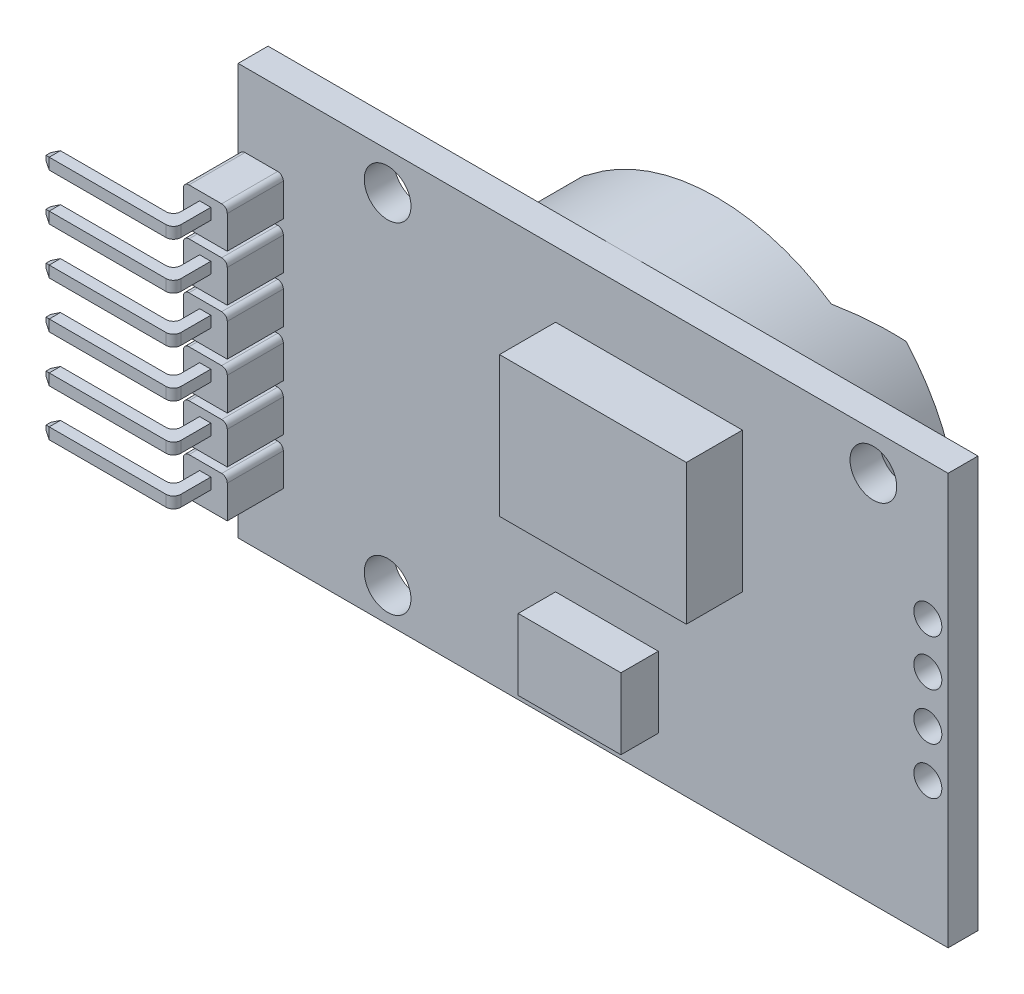
SolidWorks part; units mm, degrees
ref_plane "Front Plane" through (0, 0, 0) normal (0, 0, 1) x (1, 0, 0)
ref_plane "Top Plane" through (0, 0, 0) normal (0, 1, 0) x (1, 0, 0)
ref_plane "Right Plane" through (0, 0, 0) normal (1, 0, 0) x (0, 0, -1)
sketch "Sketch1" plane through (0, 0, 0) normal (0, 0, 1) x (1, 0, 0)
  line L1 (-19, -11) -> (19, -11)
  line L2 (-19, -11) -> (-19, 11)
  line L3 (-19, 11) -> (19, 11)
  line L4 (19, -11) -> (19, 11)
  line L5 (-19, -11) -> (19, 11) construction
  line L6 (-19, 11) -> (19, -11) construction
  point P0 (0, 0)
  dimension "D1" = 38
  dimension "D2" = 22
extrude "Boss-Extrude1" add sketch "Sketch1" along normal blind 1.6
sketch "Sketch2" plane through (0, 0, 1.6) normal (0, 0, 1) x (1, 0, 0)
  line L0 (19, -11) -> (19, 11) construction
  line L1 (-2.0099, 7.497) -> (7.9901, 7.497)
  line L2 (-2.0099, 7.497) -> (-2.0099, -0.003)
  line L3 (-2.0099, -0.003) -> (7.9901, -0.003)
  line L4 (7.9901, 7.497) -> (7.9901, -0.003)
  line L5 (-2.0099, -5.003) -> (3.4901, -5.003)
  line L6 (-2.0099, -5.003) -> (-2.0099, -8.803)
  line L7 (-2.0099, -8.803) -> (3.4901, -8.803)
  line L8 (3.4901, -5.003) -> (3.4901, -8.803)
  line L9 (19, 5) -> (16.8282, 5)
  line L10 (19, 5) -> (19, -5)
  line L11 (19, -5) -> (16.8282, -5)
  line L12 (16.8282, 5) -> (16.8282, -5)
  line L13 (-19, 11) -> (-19, -11) construction
  line L14 (-21.5, -7.5) -> (-16.5, -7.5)
  line L15 (-21.5, -7.5) -> (-21.5, 7.5)
  line L16 (-21.5, 7.5) -> (-16.5, 7.5)
  line L17 (-16.5, -7.5) -> (-16.5, 7.5)
  line L18 (-21.5, -7.5) -> (-16.5, 7.5) construction
  line L19 (-21.5, 7.5) -> (-16.5, -7.5) construction
  line L20 (19, 11) -> (-19, 11) construction
  line L21 (-21.5, -0.003) -> (-16.5, -0.003)
  line L22 (-21.5, 5) -> (-16.5, 5)
  line L23 (-21.5, 2.497) -> (-16.5, 2.497)
  line L24 (-21.5, -2.503) -> (-16.5, -2.503)
  line L25 (-21.5, -5.003) -> (-16.5, -5.003)
  line L26 (-18.9321, 4.25) -> (-18.9321, 2.5)
  line L27 (-16.8821, 7.05) -> (-18.6321, 7.05)
  line L28 (-16.5821, 6.75) -> (-16.5821, 5)
  line L29 (-16.8821, 4.7) -> (-18.6321, 4.7)
  line L30 (-18.9321, 6.75) -> (-18.9321, 5)
  line L31 (-16.8821, 2.2) -> (-18.6321, 2.2)
  line L32 (-16.5821, 4.25) -> (-16.5821, 2.5)
  line L33 (-16.8821, 4.55) -> (-18.6321, 4.55)
  line L34 (-18.9321, 1.75) -> (-18.9321, 0)
  line L35 (-16.8821, -0.3) -> (-18.6321, -0.3)
  line L36 (-16.5821, 1.75) -> (-16.5821, 0)
  line L37 (-16.8821, 2.05) -> (-18.6321, 2.05)
  line L38 (-18.9321, -0.75) -> (-18.9321, -2.5)
  line L39 (-16.8821, -2.8) -> (-18.6321, -2.8)
  line L40 (-16.5821, -0.75) -> (-16.5821, -2.5)
  line L41 (-16.8821, -0.45) -> (-18.6321, -0.45)
  line L42 (-18.9321, -3.25) -> (-18.9321, -5)
  line L43 (-16.8821, -5.3) -> (-18.6321, -5.3)
  line L44 (-16.5821, -3.25) -> (-16.5821, -5)
  line L45 (-16.8821, -2.95) -> (-18.6321, -2.95)
  line L46 (-18.9321, -5.75) -> (-18.9321, -7.5)
  line L47 (-16.8821, -7.8) -> (-18.6321, -7.8)
  line L48 (-16.5821, -5.75) -> (-16.5821, -7.5)
  line L49 (-16.8821, -5.45) -> (-18.6321, -5.45)
  line L50 (23.8182, -0.0985) -> (-35.2752, -0.0985) construction
  line L51 (16.8282, 2.5) -> (19, 2.5)
  line L52 (16.8282, 0) -> (19, 0)
  line L53 (16.8282, -2.5) -> (19, -2.5)
  line L54 (-19, 11) -> (19, 11) construction
  circle A0 centre (-11, 9) radius 1.25
  circle A1 centre (15, 9) radius 1.25
  arc A2 (-18.9321, 5) -> (-18.6321, 4.7) centre (-18.6321, 5) ccw
  arc A3 (-16.5821, 5) -> (-16.8821, 4.7) centre (-16.8821, 5) cw
  arc A4 (-16.5821, 6.75) -> (-16.8821, 7.05) centre (-16.8821, 6.75) ccw
  arc A5 (-18.6321, 7.05) -> (-18.9321, 6.75) centre (-18.6321, 6.75) ccw
  arc A6 (-18.9321, 2.5) -> (-18.6321, 2.2) centre (-18.6321, 2.5) ccw
  arc A7 (-16.5821, 2.5) -> (-16.8821, 2.2) centre (-16.8821, 2.5) cw
  arc A8 (-16.5821, 4.25) -> (-16.8821, 4.55) centre (-16.8821, 4.25) ccw
  arc A9 (-18.6321, 4.55) -> (-18.9321, 4.25) centre (-18.6321, 4.25) ccw
  arc A10 (-18.9321, 0) -> (-18.6321, -0.3) centre (-18.6321, 0) ccw
  arc A11 (-16.5821, 0) -> (-16.8821, -0.3) centre (-16.8821, 0) cw
  arc A12 (-16.5821, 1.75) -> (-16.8821, 2.05) centre (-16.8821, 1.75) ccw
  arc A13 (-18.6321, 2.05) -> (-18.9321, 1.75) centre (-18.6321, 1.75) ccw
  arc A14 (-18.9321, -2.5) -> (-18.6321, -2.8) centre (-18.6321, -2.5) ccw
  arc A15 (-16.5821, -2.5) -> (-16.8821, -2.8) centre (-16.8821, -2.5) cw
  arc A16 (-16.5821, -0.75) -> (-16.8821, -0.45) centre (-16.8821, -0.75) ccw
  arc A17 (-18.6321, -0.45) -> (-18.9321, -0.75) centre (-18.6321, -0.75) ccw
  arc A18 (-18.9321, -5) -> (-18.6321, -5.3) centre (-18.6321, -5) ccw
  arc A19 (-16.5821, -5) -> (-16.8821, -5.3) centre (-16.8821, -5) cw
  arc A20 (-16.5821, -3.25) -> (-16.8821, -2.95) centre (-16.8821, -3.25) ccw
  arc A21 (-18.6321, -2.95) -> (-18.9321, -3.25) centre (-18.6321, -3.25) ccw
  arc A22 (-18.9321, -7.5) -> (-18.6321, -7.8) centre (-18.6321, -7.5) ccw
  arc A23 (-16.5821, -7.5) -> (-16.8821, -7.8) centre (-16.8821, -7.5) cw
  arc A24 (-16.5821, -5.75) -> (-16.8821, -5.45) centre (-16.8821, -5.75) ccw
  arc A25 (-18.6321, -5.45) -> (-18.9321, -5.75) centre (-18.6321, -5.75) ccw
  circle A26 centre (-11, -9.1971) radius 1.25
  circle A27 centre (17.9141, 3.7077) radius 0.75
  circle A28 centre (17.9141, 1.243) radius 0.75
  circle A29 centre (17.9141, -1.2727) radius 0.75
  circle A30 centre (17.9141, -3.7915) radius 0.75
  point P14 (-19, 0)
  point P45 (-16.5821, 4.7)
  point P48 (-16.5821, 7.05)
  point P51 (-18.9321, 7.05)
  dimension "D10" = 0.3
  dimension "D12" = 2.5
  dimension "D13" = 8
  dimension "D14" = 2
  dimension "D15" = 2.5
  dimension "D16" = 2
  dimension "D17" = 4
  dimension "D27" = 1.5
  dimension "D1" = 5
  dimension "D2" = 3.5
  dimension "D3" = 2.5
  dimension "D4" = 2.503
  dimension "D5" = 2.5
  dimension "D6" = 2.5
  dimension "D7" = 2.5
  dimension "D8" = 2.35
  dimension "D9" = 2.35
  dimension "D18" = 10
  dimension "D19" = 7.5
  dimension "D20" = 5.5
  dimension "D21" = 3.8
  dimension "D22" = 10
  dimension "D23" = 2.5
  dimension "D24" = 2.5
  dimension "D25" = 2.5
  dimension "D26" = 6
  dimension "D11" = 6
extrude "Boss-Extrude2" add sketch "Sketch2" along normal blind 3 contours L27 A5 L30 A2 L29 A3 L28 A4 | L33 A9 L26 A6 L31 A7 L32 A8 | L37 A13 L34 A10 L35 A11 L36 A12 | L41 A17 L38 A14 L39 A15 L40 A16 | L45 A21 L42 A18 L43 A19 L44 A20 | L49 A25 L46 A22 L47 A23 L48 A24 region at (-17.7571, -6.4827, 1.6) region at (-17.7571, -3.9842, 1.6) region at (-17.7571, -1.4842, 1.6) region at (-17.7571, 1.0158, 1.6) region at (-17.7571, 3.5158, 1.6) region at (-17.7571, 6.0173, 1.6)
ref_plane "Plane1" through (0, 0, 3.1) normal (0, 0, 1) x (1, 0, 0)
sketch "Sketch3" plane through (0, 0, 3.1) normal (0, 0, 1) x (1, 0, 0)
  line L1 (-18.062, -5.9038) -> (-17.462, -5.9038)
  line L2 (-18.062, -5.9038) -> (-18.062, -6.5038)
  line L3 (-18.062, -6.5038) -> (-17.462, -6.5038)
  line L4 (-17.462, -5.9038) -> (-17.462, -6.5038)
  line L5 (-18.062, -5.9038) -> (-17.462, -6.5038) construction
  line L6 (-18.062, -6.5038) -> (-17.462, -5.9038) construction
  point P0 (-17.762, -6.2038)
  dimension "D1" = 0.6
  dimension "D2" = 0.6
extrude "Boss-Extrude3" add sketch "Sketch3" along normal mid plane 7
sketch "Sketch4" plane through (0, -6.5038, 0) normal (0, -1, 0) x (1, 0, 0)
  line L0 (-17.462, 6.6) -> (-24.462, 6.6)
  line L2 (-17.462, 6) -> (-24.462, 6)
  line L3 (-24.462, 6.6) -> (-24.462, 6)
  line M4 (-18.062, 6.6) -> (-18.062, 4.6)
  dimension "D1" = 0.6
extrude "Boss-Extrude4" add sketch "Sketch4" against normal blind 0.6 contours L0 L3 L2 M4 region at (-21.262, -6.5038, 6.3)
fillet "Fillet1" radius 0.4 2 edges at (-18.062, -6.2038, 6) (-17.462, -6.2038, 6.6)
sketch "Sketch5" plane through (0, -6.5038, 0) normal (0, -1, 0) x (1, 0, 0)
  line L0 (-24.462, 6.3) -> (-24.462, 6.4217)
  line L1 (-24.462, 6.6) -> (-24.462, 6) construction
  line L2 (-24.462, 6.4217) -> (-24.112, 6.6)
  line L3 (-24.462, 6.6) -> (-17.862, 6.6) construction
  line L4 (-24.112, 6.6) -> (-24.112, 6)
  line L5 (-18.462, 6) -> (-24.462, 6) construction
  line L6 (-24.112, 6) -> (-24.462, 6.1783)
  line L7 (-24.462, 6.1783) -> (-24.462, 6.3)
  line M8 (-17.862, 6.6) -> (-24.462, 6.6)
  line M9 (-24.462, 6.6) -> (-24.462, 6)
  line M10 (-24.462, 6) -> (-18.462, 6)
  dimension "D1" = 63
  dimension "D2" = 0.6
  dimension "D3" = 0.35
  dimension "D4" = 63
extrude "Cut-Extrude1" cut sketch "Sketch5" against normal blind 0.6 contours L2 M9 M8 | L6 M10 M9 region at (-24.3453, -6.5038, 6.5406) region at (-24.3453, -6.5038, 6.0594)
sketch "Sketch6" plane through (0, 0, 6.6) normal (0, 0, 1) x (1, 0, 0)
  line L0 (-24.112, -6.5038) -> (-24.112, -5.9038)
  line L1 (-24.112, -5.9038) -> (-24.462, -6.0822)
  line L2 (-24.462, -5.9038) -> (-24.462, -6.5038) construction
  line L3 (-24.462, -6.0822) -> (-24.462, -6.3255)
  line L4 (-24.462, -6.3255) -> (-24.112, -6.5038)
  line L6 (-24.112, -6.5038) -> (-24.462, -6.5038)
  line L7 (-24.112, -6.5038) -> (-24.112, -5.9038)
  line L8 (-24.112, -5.9038) -> (-24.462, -5.9038)
  line L9 (-24.462, -6.5038) -> (-24.462, -5.9038)
  dimension "D1" = 63
  dimension "D2" = 63
extrude "Cut-Extrude2" cut sketch "Sketch6" against normal blind 0.6 contours L9 L1 L8 | L9 L6 L4 region at (-24.3453, -6.4444, 6.6) region at (-24.3453, -5.9633, 6.6)
pattern_linear "LPattern1" count 1 spacing 10 along (1, 0, 0) count 6 spacing 2.5 along (0, 1, 0) of "Boss-Extrude3", "Boss-Extrude4", "Fillet1", "Cut-Extrude1", "Cut-Extrude2"
extrude "Cut-Extrude3" cut sketch "Sketch2<3>" against normal blind 9.6 contours A26 | A1 | A0 region at (15, 9, 1.6) region at (-11, -9.1971, 1.6)
sketch "Sketch2<3>" plane through (0, 0, 1.6) normal (0, 0, 1) x (1, 0, 0) same geometry as "Sketch2"
extrude "Boss-Extrude5" add sketch "Sketch2<4>" along normal blind 3 contours L4 L1 L2 L3 region at (2.9901, 3.747, 1.6)
sketch "Sketch2<4>" plane through (0, 0, 1.6) normal (0, 0, 1) x (1, 0, 0) same geometry as "Sketch2"
sketch "Sketch7" plane through (0, 0, 1.6) normal (0, 0, 1) x (1, 0, 0)
extrude "Boss-Extrude6" add sketch "Sketch2<5>" along normal blind 2 contours L8 L5 L6 L7 region at (0.7401, -6.903, 1.6)
sketch "Sketch2<5>" plane through (0, 0, 1.6) normal (0, 0, 1) x (1, 0, 0) same geometry as "Sketch2"
extrude "Cut-Extrude4" cut sketch "Sketch2<6>" against normal blind 4 contours A27 | A28 | A29 | A30 region at (17.9141, 3.7077, 1.6) region at (17.9141, 1.243, 1.6) region at (17.9141, -1.2727, 1.6) region at (17.9141, -3.7915, 1.6)
sketch "Sketch2<6>" plane through (0, 0, 1.6) normal (0, 0, 1) x (1, 0, 0) same geometry as "Sketch2"
sketch "Sketch8" plane through (0, 0, 0) normal (0, 0, -1) x (-1, 0, 0)
  circle A0 centre (0, 0) radius 10
  circle A1 centre (0, 0) radius 11
  dimension "D1" = 20
  dimension "D2" = 1
extrude "Boss-Extrude7" add sketch "Sketch8" along normal blind 7
sketch "Sketch9" plane through (0, -11, 0) normal (0, -1, 0) x (1, 0, 0)
  line L0 (-15.2619, -5) -> (18.4994, -5)
  line L1 (0, 0) -> (19, 0) construction
  line L2 (0, -5) -> (-6.8328, -5)
  line L3 (-6.8328, -5) -> (-10.4228, -7)
  line L4 (-11, -7) -> (11, -7) construction
  line L5 (6.1488, -5) -> (8.1488, -7)
  line L6 (8.1488, -7) -> (-11, -7)
  dimension "D1" = 5
extrude "Cut-Extrude5" cut sketch "Sketch9" against normal through all contours L6 L5 L0 region at (-0.763, -11, -6.0591)
sketch "Sketch10" plane through (0, 0, -7) normal (0, 0, -1) x (-1, 0, 0)
  line L0 (10.4228, 3.5164) -> (10.4228, -3.5164)
  line L1 (6.7, -3.5164) -> (13.3, -3.5164)
  line L2 (6.7, -3.5164) -> (6.7, 3.5164)
  line L3 (6.7, 3.5164) -> (13.3, 3.5164)
  line L4 (13.3, -3.5164) -> (13.3, 3.5164)
  line L5 (6.7, -3.5164) -> (13.3, 3.5164) construction
  line L6 (6.7, 3.5164) -> (13.3, -3.5164) construction
  line L7 (10.4228, 3.5164) -> (10.4228, -3.5164) construction
  line L8 (12.3, -2.5164) -> (12.3, 2.5164)
  line L9 (7.7, 2.5164) -> (12.3, 2.5164)
  line L10 (7.7, -2.5164) -> (7.7, 2.5164)
  line L11 (7.7, -2.5164) -> (12.3, -2.5164)
  arc A0 (6.8328, -7.3015) -> (6.8328, 7.3015) centre (0, 0) ccw construction
  arc A1 (10.4228, -3.5164) -> (10.4228, 3.5164) centre (0, 0) ccw
  point P0 (10, 0)
  arc M2 (10.4228, -3.5164) -> (10.4228, 3.5164) centre (0, 0) ccw
  dimension "D1" = 6.6
  dimension "D2" = 1
extrude "Boss-Extrude8" add sketch "Sketch10" against normal up to surface (7 mm away) contours L11 L1 L4 L3 L9 L8 M2 region at (-12.3506, 0, -7) up to face at (-12.25, 9, 0)
sketch "Sketch11" plane through (0, 0, -7) normal (0, 0, -1) x (-1, 0, 0)
  line L0 (10.7083, 2.5164) -> (12.3, 2.5164) construction
  line L1 (11.5042, 2.5164) -> (8.8861, 2.5164)
  line L2 (11.5042, 2.5164) -> (11.5042, -2.4974)
  line L3 (11.5042, -2.4974) -> (8.8861, -2.4974)
  line L4 (8.8861, 2.5164) -> (8.8861, -2.4974)
extrude "Cut-Extrude6" cut sketch "Sketch11" against normal blind 7
sketch "Sketch12" plane through (0, 0, 0) normal (0, 0, -1) x (-1, 0, 0)
  circle A0 centre (0, 0) radius 9.75
  dimension "D1" = 19.5
extrude "Boss-Extrude9" add sketch "Sketch12" along normal blind 6
fillet "Fillet2" radius 0.52 1 edges at (-9.75, 0, -6)
sketch "Sketch13" plane through (0, 0, -6) normal (0, 0, -1) x (-1, 0, 0)
  line L0 (0, 7.4746) -> (0, 3.4746)
  line L1 (-2, 5.8779) -> (2, 5.8779)
  line L2 (-0.125, 7.4746) -> (-0.125, 3.4746)
  line L3 (-2, 5.7529) -> (2, 5.7529)
  line L4 (-0.125, 7.4746) -> (0, 7.4746)
  line L5 (2, 5.8779) -> (2, 5.7529)
  line L6 (0, 3.4746) -> (-0.125, 3.4746)
  line L7 (-2, 5.8779) -> (-2, 5.7529)
  line L8 (-4.1554, -1.5783) -> (4.0432, -1.5783) construction
  line L9 (-6.6341, -3.7709) -> (6.3948, -3.7709) construction
  line L10 (-1.2319, -6.7263) -> (0.9926, -6.7263) construction
  text T0 " CR2032" font "Century Gothic" height 2.5
  text T1 "   Lithium cell" font "Century Gothic" height in points 5
  text T2 "3V" font "Century Gothic" height in points 8
  dimension "D1" = 4
  dimension "D2" = 4
  dimension "D3" = 0.125
  dimension "D4" = 0.125
